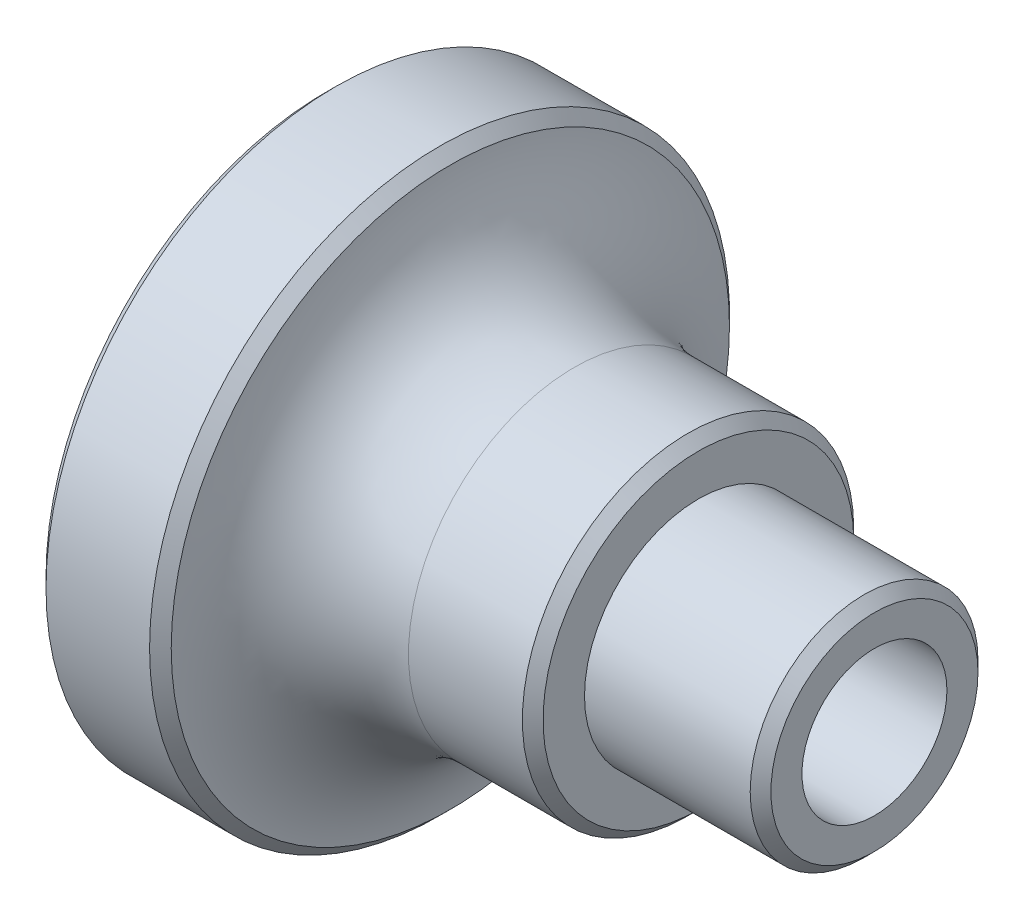
SolidWorks part; units mm, degrees
ref_plane "Front Plane" through (0, 0, 0) normal (0, 0, 1) x (1, 0, 0)
ref_plane "Top Plane" through (0, 0, 0) normal (0, 1, 0) x (1, 0, 0)
ref_plane "Right Plane" through (0, 0, 0) normal (1, 0, 0) x (0, 0, -1)
sketch "Sketch1" plane through (0, 0, 0) normal (1, 0, 0) x (0, 0, -1)
  circle A0 centre (0, 0) radius 1.75
  circle A1 centre (0, 0) radius 7
  dimension "D1" = 14
  dimension "D2" = 3.5
extrude "Boss-Extrude1" add sketch "Sketch1" along normal blind 3
sketch "Sketch2" plane through (3, 0, 0) normal (1, 0, 0) x (0, 0, -1)
  circle A0 centre (0, 0) radius 1.75 construction
  circle A1 centre (0, 0) radius 1.75
  circle A2 centre (0, 0) radius 4
  dimension "D1" = 8
extrude "Boss-Extrude2" add sketch "Sketch2" along normal offset from surface (6 mm away) 9
fillet "Fillet1" radius 3 1 edges at (3, 0, -4)
sketch "Sketch4" plane through (9, 0, 0) normal (1, 0, 0) x (0, 0, -1)
  circle A0 centre (0, 0) radius 1.75 construction
  circle A1 centre (0, 0) radius 1.75
  circle A2 centre (0, 0) radius 2.75
  dimension "D1" = 5.5
extrude "Boss-Extrude3" add sketch "Sketch4" along normal blind 4.25
chamfer "Chamfer1" distance 0.25 angle 45 5 edges at (0, 0, -1.75) (0, 0, -7) (3, 0, -7) (13.25, 0, -2.75) (9, 0, -4)
sketch "Sketch3" [suppressed] plane through (9, 0, 0) normal (1, 0, 0) x (0, 0, -1)
  line L0 (0, -2.75) -> (0, -7)
  line L1 (2.75, 0) -> (7, 0)
  line L2 (7, 0) -> (-7, 0) construction
  circle A0 centre (0, 0) radius 7 construction
  arc A1 (0, -7) -> (7, 0) centre (0, 0) ccw
  circle A2 centre (0, 0) radius 2.75 construction
  arc A3 (0, -2.75) -> (2.75, 0) centre (0, 0) ccw
  circle A4 centre (0, 0) radius 2.75 construction
  circle A5 centre (0, 0) radius 7 construction
  point P15 (7, 0)
extrude "Cut-Extrude1" [suppressed] cut sketch "Sketch3" against normal blind 5
fillet "Fillet2" [suppressed] radius 1.5
fillet "Fillet3" [suppressed] radius 0.5
